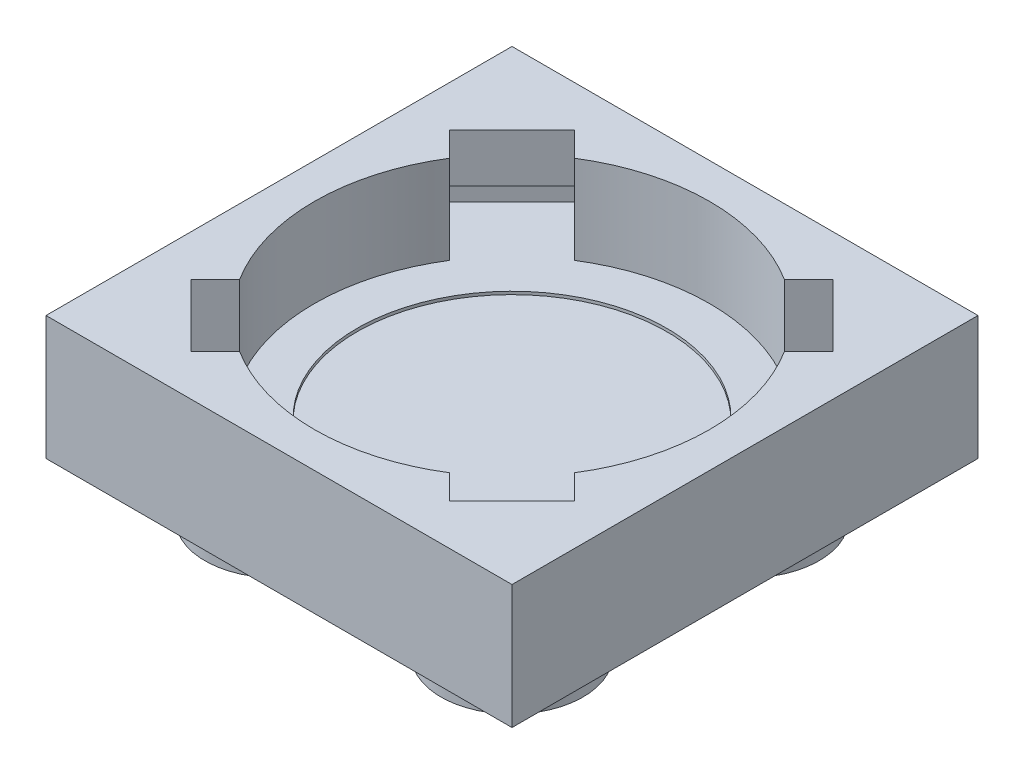
SolidWorks part; units mm, degrees
ref_plane "Front Plane" through (0, 0, 0) normal (0, 0, 1) x (1, 0, 0)
ref_plane "Top Plane" through (0, 0, 0) normal (0, 1, 0) x (1, 0, 0)
ref_plane "Right Plane" through (0, 0, 0) normal (1, 0, 0) x (0, 0, -1)
sketch "Sketch2" plane through (0, 0, 0) normal (0, 1, 0) x (1, 0, 0)
  line L1 (0, 0) -> (15.8, 0)
  line L2 (0, 0) -> (0, 15.8)
  line L3 (0, 15.8) -> (15.8, 15.8)
  line L4 (15.8, 0) -> (15.8, 15.8)
  dimension "D1" = 15.8
  dimension "D2" = 15.8
extrude "Boss-Extrude2" add sketch "Sketch2" against normal blind 4.2
sketch "Sketch4" plane through (0, 0, 0) normal (0, 1, 0) x (1, 0, 0)
  line L0 (15.8, 0) -> (15.8, 15.8) construction
  line L1 (14.6, 14.6) -> (1.2, 14.6)
  line L2 (14.6, 14.6) -> (14.6, 1.2)
  line L3 (14.6, 1.2) -> (1.2, 1.2)
  line L4 (1.2, 14.6) -> (1.2, 1.2)
  line L5 (0, -55) -> (0, 55) construction
  line L6 (-55, 0) -> (55, 0) construction
  line L7 (15.8, 15.8) -> (0, 15.8) construction
  dimension "D1" = 1.2
  dimension "D2" = 1.2
  dimension "D3" = 1.2
  dimension "D4" = 1.2
extrude "Cut-Extrude1" cut sketch "Sketch4" against normal offset from surface (3 mm away) 1.2 up to face at (7.9, -4.2, -7.9)
sketch "Sketch6" plane through (0, -4.2, 0) normal (0, -1, 0) x (-1, 0, 0)
  line L0 (-15.8, 0) -> (-15.8, 15.8) construction
  line L1 (-15.8, 15.8) -> (0, 15.8) construction
  circle A0 centre (-11.9, 11.9) radius 2.41
  dimension "D1" = 4.82
  dimension "D2" = 3.9
  dimension "D3" = 3.9
extrude "Boss-Extrude4" add sketch "Sketch6" along normal blind 1.8
pattern_linear "LPattern1" count 2 spacing 8 along (0, 0, 1) count 2 spacing 8 along (-1, 0, 0) of "Boss-Extrude4"
sketch "Sketch8" plane through (0, -3, 0) normal (0, 1, 0) x (1, 0, 0)
  line L0 (0, -2.31) -> (0, 2.31) construction
  line L1 (-2.31, 0) -> (2.31, 0) construction
  circle A0 centre (7.9, 7.9) radius 5.25
  point P27 (7.9, 7.9)
  dimension "D1" = 10.5
  dimension "D2" = 7.9
  dimension "D3" = 7.9
extrude "Cut-Extrude2" cut sketch "Sketch8" against normal blind 0.1
sketch "Sketch11" plane through (0, -3, 0) normal (0, 1, 0) x (1, 0, 0)
  line L1 (1.2, 14.6) -> (14.6, 14.6)
  line L2 (1.2, 14.6) -> (1.2, 1.2)
  line L3 (1.2, 1.2) -> (14.6, 1.2)
  line L4 (14.6, 14.6) -> (14.6, 1.2)
  circle A0 centre (7.9, 7.9) radius 6.7
  line M3 (14.6, 1.2) -> (14.6, 14.6)
  line M4 (14.6, 14.6) -> (1.2, 14.6)
  line M5 (1.2, 14.6) -> (1.2, 1.2)
  line M6 (1.2, 1.2) -> (14.6, 1.2)
extrude "Boss-Extrude9" add sketch "Sketch11" along normal up to surface (3 mm away) contours A0 L1 M5 | A0 L4 M4 | A0 L2 M6 | A0 L3 M3 region at (2.6966, -3, -13.1034) region at (13.1034, -3, -13.1034) region at (2.6966, -3, -2.6966) region at (13.1034, -3, -2.6966) up to face at (7.9, 0, -7.9)
sketch "Sketch12" plane through (0, 0, 0) normal (0, 1, 0) x (1, 0, 0)
  line L0 (0, 15.8) -> (3.1624, 12.6376)
  line L1 (0, -2.31) -> (0, 2.31) construction
  line L2 (15.8, 15.8) -> (0, 15.8) construction
  line L3 (2.1017, 11.577) -> (4.223, 13.6983)
  line L4 (2.1017, 11.577) -> (4.223, 13.6983)
  line L5 (2.1017, 11.577) -> (1.3946, 12.2841)
  line L6 (4.223, 13.6983) -> (3.5159, 14.4054)
  line L7 (1.3946, 12.2841) -> (3.5159, 14.4054)
  line L8 (2.1017, 11.577) -> (4.223, 13.6983)
  line L9 (2.1017, 11.577) -> (2.4236, 11.2551)
  line L10 (4.223, 13.6983) -> (4.5449, 13.3764)
  line L11 (2.4236, 11.2551) -> (4.5449, 13.3764)
  circle A0 centre (7.9, 7.9) radius 6.7 construction
  point P11 (3.1624, 12.6376)
  circle M2 centre (7.9, 7.9) radius 6.7
  dimension "D1" = 1
  dimension "D2" = 1.5
extrude "Cut-Extrude3" cut sketch "Sketch12" against normal offset from surface (3 mm away) 1.2 contours L7 L5 L3 L0 | L3 L9 M2 | L10 L3 M2 | L7 L0 L3 L6 | L9 L11 L10 M2 region at (3.3392, 0, -13.5215) region at (2.2785, 0, -12.4608) region at (2.4022, 0, -11.8054) region at (3.9946, 0, -13.3978) region at (3.341, 0, -12.459) up to face at (11.9, -4.2, -6.31)
ref_axis "Axis2" through (7.9, 0, -7.9) along (0, -1, 0)
sketch "Sketch20" plane through (-5.4447, 0, -5.4447) normal (0.7071, 0, 0.7071) x (0.7071, 0, -0.7071)
  line L0 (12.6723, -3) -> (12.6723, 0) construction
  line L1 (9.6723, -3) -> (12.6723, -3)
  line L2 (9.6723, -3) -> (9.6723, -1.65)
  line L3 (9.6723, -1.65) -> (12.6723, -1.65)
  line L4 (12.6723, -3) -> (12.6723, -1.65)
  line L5 (9.6723, 0) -> (12.6723, 0) construction
  dimension "D1" = 1.65
extrude "Cut-Extrude4" cut sketch "Sketch20" against normal blind 1.25
pattern_circular "CirPattern3" count 4 every 90 about axis through (7.9, 0, -7.9) along (0, -1, 0) of "Cut-Extrude3", "Cut-Extrude4"
